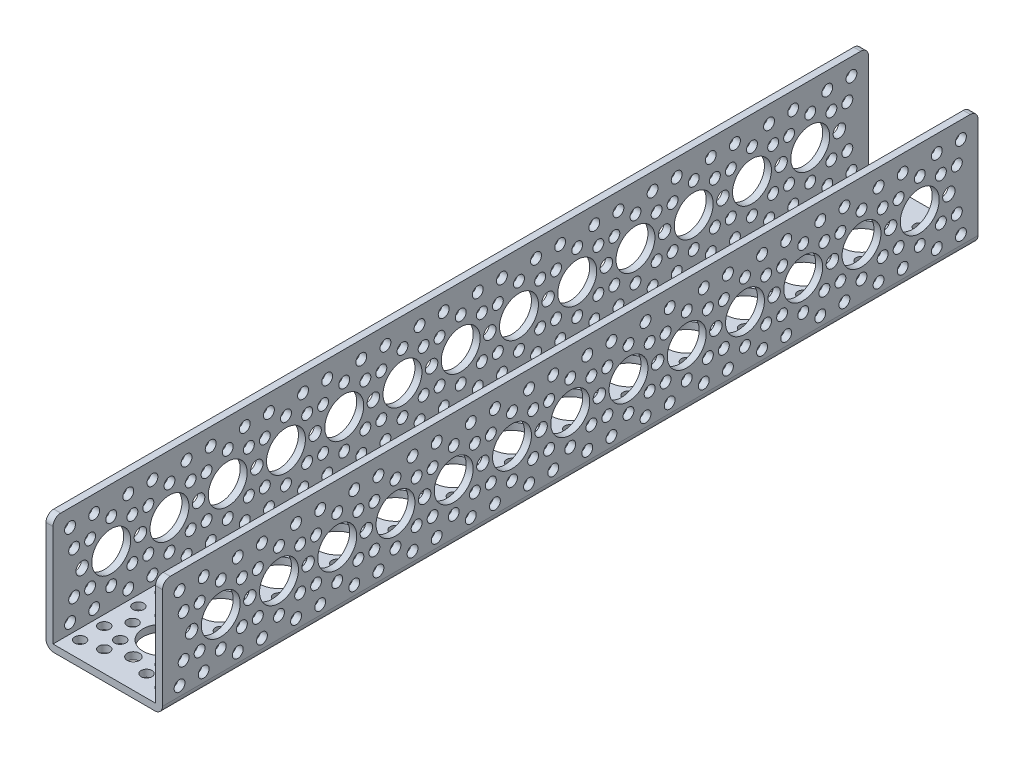
SolidWorks part; units mm, degrees
ref_plane "Front Plane" through (0, 0, 0) normal (0, 0, 1) x (1, 0, 0)
ref_plane "Top Plane" through (0, 0, 0) normal (0, 1, 0) x (1, 0, 0)
ref_plane "Right Plane" through (0, 0, 0) normal (1, 0, 0) x (0, 0, -1)
ref_plane "Plane1" through (0, 0, 0) normal (0, -1, 0) x (1, 0, 0)
sketch "Sketch1" plane through (0, 0, 0) normal (0, -1, 0) x (1, 0, 0)
  line L0 (38.1, 266.7) -> (0, 266.7)
  line L1 (0, 266.7) -> (0, 0)
  line L2 (0, 0) -> (38.1, 0)
  line L3 (38.1, 0) -> (38.1, 266.7)
extrude "Boss-Extrude1" add sketch "Sketch1" against normal blind 38.1
sketch "Sketch2" plane through (0, 0, 266.7) normal (0, 0, 1) x (1, 0, 0)
  line L0 (35.814, 38.1) -> (2.286, 38.1)
  line L1 (2.286, 38.1) -> (2.286, 2.286)
  line L2 (2.286, 2.286) -> (35.814, 2.286)
  line L3 (35.814, 2.286) -> (35.814, 38.1)
extrude "Cut-Extrude1" cut sketch "Sketch2" against normal through all
hole_wizard "Hole1" positions "Sketch4" profile "Sketch3" legacy
sketch "Sketch4" plane through (38.1, 0, 0) normal (1, 0, 0) x (0, 0, -1)
  point P0 (-38.1, 19.05)
  point P1 (-19.05, 19.05)
  point P2 (-57.15, 19.05)
  point P3 (-76.2, 19.05)
  point P4 (-95.25, 19.05)
  point P5 (-114.3, 19.05)
  point P6 (-133.35, 19.05)
  point P7 (-152.4, 19.05)
  point P8 (-171.45, 19.05)
  point P9 (-190.5, 19.05)
  point P10 (-209.55, 19.05)
  point P11 (-228.6, 19.05)
  point P12 (-247.65, 19.05)
sketch "Sketch3" plane through (38.1, 19.05, 38.1) normal (0, 1, 0) x (0, 0, -1)
  line L0 (0, 0) -> (0, 2.286)
  line L1 (0, 2.286) -> (6.3627, 2.286)
  line L2 (6.3627, 2.286) -> (6.3627, 0)
  line L3 (6.3627, 0) -> (0, 0)
  line L4 (0, 110) -> (0, -10) construction
  dimension "Diameter" = 12.7254
  dimension "Depth" = 2.286
hole_wizard "#5 Clearance Hole1" positions "Sketch6" profile "Sketch5" hole size "#5" standard "ANSI Inch"
sketch "Sketch6" plane through (38.1, 0, 0) normal (1, 0, 0) x (0, 0, -1)
  point P0 (-253.2296, 5.5796)
  point P1 (-259.7852, 12.1352)
  point P2 (-253.2296, 32.5204)
  point P3 (-259.7852, 25.9648)
  point P4 (-13.4704, 5.5796)
  point P5 (-6.9148, 12.1352)
  point P6 (-13.4704, 32.5204)
  point P7 (-6.9148, 25.9648)
  point P8 (-234.1796, 5.5796)
  point P9 (-215.1296, 5.5796)
  point P10 (-196.0796, 5.5796)
  point P11 (-177.0296, 5.5796)
  point P12 (-157.9796, 5.5796)
  point P13 (-138.9296, 5.5796)
  point P14 (-119.8796, 5.5796)
  point P15 (-100.8296, 5.5796)
  point P16 (-81.7796, 5.5796)
  point P17 (-62.7296, 5.5796)
  point P18 (-43.6796, 5.5796)
  point P19 (-24.6296, 5.5796)
  point P20 (-234.1796, 32.5204)
  point P21 (-215.1296, 32.5204)
  point P22 (-196.0796, 32.5204)
  point P23 (-177.0296, 32.5204)
  point P24 (-157.9796, 32.5204)
  point P25 (-138.9296, 32.5204)
  point P26 (-119.8796, 32.5204)
  point P27 (-100.8296, 32.5204)
  point P28 (-81.7796, 32.5204)
  point P29 (-62.7296, 32.5204)
  point P30 (-43.6796, 32.5204)
  point P31 (-24.6296, 32.5204)
  point P32 (-261.1204, 5.5796)
  point P33 (-261.1204, 32.5204)
  point P34 (-242.0704, 5.5796)
  point P35 (-242.0704, 32.5204)
  point P36 (-223.0204, 5.5796)
  point P37 (-223.0204, 32.5204)
  point P38 (-203.9704, 5.5796)
  point P39 (-203.9704, 32.5204)
  point P40 (-184.9204, 5.5796)
  point P41 (-184.9204, 32.5204)
  point P42 (-165.8704, 5.5796)
  point P43 (-165.8704, 32.5204)
  point P44 (-146.8204, 5.5796)
  point P45 (-146.8204, 32.5204)
  point P46 (-127.7704, 5.5796)
  point P47 (-127.7704, 32.5204)
  point P48 (-108.7204, 5.5796)
  point P49 (-108.7204, 32.5204)
  point P50 (-89.6704, 5.5796)
  point P51 (-89.6704, 32.5204)
  point P52 (-70.6204, 5.5796)
  point P53 (-70.6204, 32.5204)
  point P54 (-51.5704, 5.5796)
  point P55 (-51.5704, 32.5204)
  point P56 (-240.7352, 12.1352)
  point P57 (-247.65, 9.271)
  point P58 (-254.5648, 12.1352)
  point P59 (-254.5648, 25.9648)
  point P60 (-247.65, 28.829)
  point P61 (-221.6852, 12.1352)
  point P62 (-228.6, 9.271)
  point P63 (-235.5148, 12.1352)
  point P64 (-235.5148, 25.9648)
  point P65 (-228.6, 28.829)
  point P66 (-202.6352, 12.1352)
  point P67 (-209.55, 9.271)
  point P68 (-216.4648, 12.1352)
  point P69 (-216.4648, 25.9648)
  point P70 (-209.55, 28.829)
  point P71 (-183.5852, 12.1352)
  point P72 (-190.5, 9.271)
  point P73 (-197.4148, 12.1352)
  point P74 (-197.4148, 25.9648)
  point P75 (-190.5, 28.829)
  point P76 (-164.5352, 12.1352)
  point P77 (-171.45, 9.271)
  point P78 (-178.3648, 12.1352)
  point P79 (-178.3648, 25.9648)
  point P80 (-171.45, 28.829)
  point P81 (-145.4852, 12.1352)
  point P82 (-152.4, 9.271)
  point P83 (-159.3148, 12.1352)
  point P84 (-159.3148, 25.9648)
  point P85 (-152.4, 28.829)
  point P86 (-126.4352, 12.1352)
  point P87 (-133.35, 9.271)
  point P88 (-140.2648, 12.1352)
  point P89 (-140.2648, 25.9648)
  point P90 (-133.35, 28.829)
  point P91 (-107.3852, 12.1352)
  point P92 (-114.3, 9.271)
  point P93 (-121.2148, 12.1352)
  point P94 (-121.2148, 25.9648)
  point P95 (-114.3, 28.829)
  point P96 (-88.3352, 12.1352)
  point P97 (-95.25, 9.271)
  point P98 (-102.1648, 12.1352)
  point P99 (-102.1648, 25.9648)
  point P100 (-95.25, 28.829)
  point P101 (-69.2852, 12.1352)
  point P102 (-76.2, 9.271)
  point P103 (-83.1148, 12.1352)
  point P104 (-83.1148, 25.9648)
  point P105 (-76.2, 28.829)
  point P106 (-50.2352, 12.1352)
  point P107 (-57.15, 9.271)
  point P108 (-64.0648, 12.1352)
  point P109 (-64.0648, 25.9648)
  point P110 (-57.15, 28.829)
  point P111 (-31.1852, 12.1352)
  point P112 (-38.1, 9.271)
  point P113 (-45.0148, 12.1352)
  point P114 (-45.0148, 25.9648)
  point P115 (-38.1, 28.829)
  point P116 (-240.7352, 25.9648)
  point P117 (-221.6852, 25.9648)
  point P118 (-202.6352, 25.9648)
  point P119 (-183.5852, 25.9648)
  point P120 (-164.5352, 25.9648)
  point P121 (-145.4852, 25.9648)
  point P122 (-126.4352, 25.9648)
  point P123 (-107.3852, 25.9648)
  point P124 (-88.3352, 25.9648)
  point P125 (-69.2852, 25.9648)
  point P126 (-50.2352, 25.9648)
  point P127 (-31.1852, 25.9648)
  point P128 (-32.5204, 5.5796)
  point P129 (-32.5204, 32.5204)
  point P130 (-5.5796, 5.5796)
  point P131 (-5.5796, 32.5204)
  point P132 (-12.1352, 12.1352)
  point P133 (-19.05, 9.271)
  point P134 (-25.9648, 12.1352)
  point P135 (-25.9648, 25.9648)
  point P136 (-19.05, 28.829)
  point P137 (-12.1352, 25.9648)
sketch "Sketch5" plane through (38.1, 5.5796, 253.2296) normal (0, 1, 0) x (0, 0, -1)
  line L0 (0, 0) -> (0, 2.286)
  line L1 (0, 2.286) -> (1.778, 2.286)
  line L2 (1.778, 2.286) -> (1.778, 0)
  line L5 (1.778, 0) -> (0, 0)
  line L11 (0, -6.35) -> (0, 107.95) construction
  dimension "Thru Hole Dia." = 3.556
  dimension "Thru Hole Depth" = 2.286
hole_wizard "#6 Clearance Hole1" positions "Sketch8" profile "Sketch7" hole size "#6" standard "ANSI Inch"
sketch "Sketch8" plane through (38.1, 0, 0) normal (1, 0, 0) x (0, 0, -1)
  point P0 (-257.175, 19.05)
  point P1 (-238.125, 19.05)
  point P2 (-219.075, 19.05)
  point P3 (-200.025, 19.05)
  point P4 (-180.975, 19.05)
  point P5 (-161.925, 19.05)
  point P6 (-142.875, 19.05)
  point P7 (-123.825, 19.05)
  point P8 (-104.775, 19.05)
  point P9 (-85.725, 19.05)
  point P10 (-66.675, 19.05)
  point P11 (-47.625, 19.05)
  point P12 (-28.575, 19.05)
  point P13 (-9.525, 19.05)
sketch "Sketch7" plane through (38.1, 19.05, 257.175) normal (0, 1, 0) x (0, 0, -1)
  line L0 (0, 0) -> (0, 2.286)
  line L1 (0, 2.286) -> (2.032, 2.286)
  line L2 (2.032, 2.286) -> (2.032, 0)
  line L5 (2.032, 0) -> (0, 0)
  line L11 (0, -6.35) -> (0, 107.95) construction
  dimension "Thru Hole Dia." = 4.064
  dimension "Thru Hole Depth" = 2.286
hole_wizard "Hole2" positions "Sketch10" profile "Sketch9" legacy
sketch "Sketch10" plane through (0, 0, 0) normal (0, -1, 0) x (-1, 0, 0)
  point P0 (-19.05, -247.65)
  point P1 (-19.05, -228.6)
  point P2 (-19.05, -209.55)
  point P3 (-19.05, -190.5)
  point P4 (-19.05, -171.45)
  point P5 (-19.05, -152.4)
  point P6 (-19.05, -133.35)
  point P7 (-19.05, -114.3)
  point P8 (-19.05, -95.25)
  point P9 (-19.05, -76.2)
  point P10 (-19.05, -57.15)
  point P11 (-19.05, -38.1)
  point P12 (-19.05, -19.05)
sketch "Sketch9" plane through (19.05, 0, 247.65) normal (1, 0, 0) x (0, 0, -1)
  line L0 (0, 0) -> (0, 38.1)
  line L1 (0, 38.1) -> (6.3627, 38.1)
  line L2 (6.3627, 38.1) -> (6.3627, 0)
  line L3 (6.3627, 0) -> (0, 0)
  line L4 (0, 110) -> (0, -10) construction
  dimension "Diameter" = 12.7254
  dimension "Depth" = 38.1
hole_wizard "#6 Clearance Hole2" positions "Sketch12" profile "Sketch11" hole size "#6" standard "ANSI Inch"
sketch "Sketch12" plane through (0, 0, 0) normal (0, -1, 0) x (-1, 0, 0)
  point P0 (-19.05, -257.175)
  point P1 (-19.05, -238.125)
  point P2 (-19.05, -219.075)
  point P3 (-19.05, -200.025)
  point P4 (-19.05, -180.975)
  point P5 (-19.05, -161.925)
  point P6 (-19.05, -142.875)
  point P7 (-19.05, -123.825)
  point P8 (-19.05, -104.775)
  point P9 (-19.05, -85.725)
  point P10 (-19.05, -66.675)
  point P11 (-19.05, -47.625)
  point P12 (-19.05, -28.575)
  point P13 (-19.05, -9.525)
sketch "Sketch11" plane through (19.05, 0, 257.175) normal (1, 0, 0) x (0, 0, -1)
  line L0 (0, 0) -> (0, 38.1)
  line L1 (0, 38.1) -> (2.032, 38.1)
  line L2 (2.032, 38.1) -> (2.032, 0)
  line L5 (2.032, 0) -> (0, 0)
  line L11 (0, -6.35) -> (0, 107.95) construction
  dimension "Thru Hole Dia." = 4.064
  dimension "Thru Hole Depth" = 38.1
hole_wizard "#5 Clearance Hole2" positions "Sketch14" profile "Sketch13" hole size "#5" standard "ANSI Inch"
sketch "Sketch14" plane through (0, 0, 0) normal (0, -1, 0) x (-1, 0, 0)
  point P0 (-5.5796, -261.1204)
  point P1 (-5.5796, -253.2296)
  point P2 (-12.1352, -259.7852)
  point P3 (-32.5204, -261.1204)
  point P4 (-32.5204, -253.2296)
  point P5 (-25.9648, -259.7852)
  point P6 (-5.5796, -242.0704)
  point P7 (-5.5796, -234.1796)
  point P8 (-32.5204, -242.0704)
  point P9 (-32.5204, -234.1796)
  point P10 (-5.5796, -223.0204)
  point P11 (-5.5796, -215.1296)
  point P12 (-32.5204, -223.0204)
  point P13 (-32.5204, -215.1296)
  point P14 (-5.5796, -203.9704)
  point P15 (-5.5796, -196.0796)
  point P16 (-32.5204, -203.9704)
  point P17 (-32.5204, -196.0796)
  point P18 (-5.5796, -184.9204)
  point P19 (-5.5796, -177.0296)
  point P20 (-32.5204, -184.9204)
  point P21 (-32.5204, -177.0296)
  point P22 (-5.5796, -165.8704)
  point P23 (-5.5796, -157.9796)
  point P24 (-32.5204, -165.8704)
  point P25 (-32.5204, -157.9796)
  point P26 (-5.5796, -146.8204)
  point P27 (-5.5796, -138.9296)
  point P28 (-32.5204, -146.8204)
  point P29 (-32.5204, -138.9296)
  point P30 (-5.5796, -127.7704)
  point P31 (-5.5796, -119.8796)
  point P32 (-32.5204, -127.7704)
  point P33 (-32.5204, -119.8796)
  point P34 (-5.5796, -108.7204)
  point P35 (-5.5796, -100.8296)
  point P36 (-32.5204, -108.7204)
  point P37 (-32.5204, -100.8296)
  point P38 (-5.5796, -89.6704)
  point P39 (-5.5796, -81.7796)
  point P40 (-32.5204, -89.6704)
  point P41 (-32.5204, -81.7796)
  point P42 (-5.5796, -70.6204)
  point P43 (-5.5796, -62.7296)
  point P44 (-32.5204, -70.6204)
  point P45 (-32.5204, -62.7296)
  point P46 (-5.5796, -51.5704)
  point P47 (-5.5796, -43.6796)
  point P48 (-32.5204, -51.5704)
  point P49 (-32.5204, -43.6796)
  point P50 (-12.1352, -240.7352)
  point P51 (-9.271, -247.65)
  point P52 (-12.1352, -254.5648)
  point P53 (-25.9648, -254.5648)
  point P54 (-28.829, -247.65)
  point P55 (-25.9648, -240.7352)
  point P56 (-12.1352, -221.6852)
  point P57 (-9.271, -228.6)
  point P58 (-12.1352, -235.5148)
  point P59 (-25.9648, -235.5148)
  point P60 (-28.829, -228.6)
  point P61 (-25.9648, -221.6852)
  point P62 (-12.1352, -202.6352)
  point P63 (-9.271, -209.55)
  point P64 (-12.1352, -216.4648)
  point P65 (-25.9648, -216.4648)
  point P66 (-28.829, -209.55)
  point P67 (-25.9648, -202.6352)
  point P68 (-12.1352, -183.5852)
  point P69 (-9.271, -190.5)
  point P70 (-12.1352, -197.4148)
  point P71 (-25.9648, -197.4148)
  point P72 (-28.829, -190.5)
  point P73 (-25.9648, -183.5852)
  point P74 (-12.1352, -164.5352)
  point P75 (-9.271, -171.45)
  point P76 (-12.1352, -178.3648)
  point P77 (-25.9648, -178.3648)
  point P78 (-28.829, -171.45)
  point P79 (-25.9648, -164.5352)
  point P80 (-12.1352, -145.4852)
  point P81 (-9.271, -152.4)
  point P82 (-12.1352, -159.3148)
  point P83 (-25.9648, -159.3148)
  point P84 (-28.829, -152.4)
  point P85 (-25.9648, -145.4852)
  point P86 (-12.1352, -126.4352)
  point P87 (-9.271, -133.35)
  point P88 (-12.1352, -140.2648)
  point P89 (-25.9648, -140.2648)
  point P90 (-28.829, -133.35)
  point P91 (-25.9648, -126.4352)
  point P92 (-12.1352, -107.3852)
  point P93 (-9.271, -114.3)
  point P94 (-12.1352, -121.2148)
  point P95 (-25.9648, -121.2148)
  point P96 (-28.829, -114.3)
  point P97 (-25.9648, -107.3852)
  point P98 (-12.1352, -88.3352)
  point P99 (-9.271, -95.25)
  point P100 (-12.1352, -102.1648)
  point P101 (-25.9648, -102.1648)
  point P102 (-28.829, -95.25)
  point P103 (-25.9648, -88.3352)
  point P104 (-12.1352, -69.2852)
  point P105 (-9.271, -76.2)
  point P106 (-12.1352, -83.1148)
  point P107 (-25.9648, -83.1148)
  point P108 (-28.829, -76.2)
  point P109 (-25.9648, -69.2852)
  point P110 (-12.1352, -50.2352)
  point P111 (-9.271, -57.15)
  point P112 (-12.1352, -64.0648)
  point P113 (-25.9648, -64.0648)
  point P114 (-28.829, -57.15)
  point P115 (-25.9648, -50.2352)
  point P116 (-9.271, -38.1)
  point P117 (-12.1352, -45.0148)
  point P118 (-25.9648, -45.0148)
  point P119 (-28.829, -38.1)
  point P120 (-5.5796, -32.5204)
  point P121 (-5.5796, -24.6296)
  point P122 (-12.1352, -31.1852)
  point P123 (-32.5204, -32.5204)
  point P124 (-32.5204, -24.6296)
  point P125 (-25.9648, -31.1852)
  point P126 (-5.5796, -5.5796)
  point P127 (-5.5796, -13.4704)
  point P128 (-12.1352, -6.9148)
  point P129 (-32.5204, -5.5796)
  point P130 (-32.5204, -13.4704)
  point P131 (-25.9648, -6.9148)
  point P132 (-12.1352, -12.1352)
  point P133 (-9.271, -19.05)
  point P134 (-12.1352, -25.9648)
  point P135 (-25.9648, -25.9648)
  point P136 (-28.829, -19.05)
  point P137 (-25.9648, -12.1352)
sketch "Sketch13" plane through (5.5796, 0, 261.1204) normal (1, 0, 0) x (0, 0, -1)
  line L0 (0, 0) -> (0, 38.1)
  line L1 (0, 38.1) -> (1.778, 38.1)
  line L2 (1.778, 38.1) -> (1.778, 0)
  line L5 (1.778, 0) -> (0, 0)
  line L11 (0, -6.35) -> (0, 107.95) construction
  dimension "Thru Hole Dia." = 3.556
  dimension "Thru Hole Depth" = 38.1
hole_wizard "Hole3" positions "Sketch16" profile "Sketch15" legacy
sketch "Sketch16" plane through (0, 0, 0) normal (-1, 0, 0) x (0, 0, 1)
  point P0 (38.1, 19.05)
  point P1 (19.05, 19.05)
  point P2 (57.15, 19.05)
  point P3 (76.2, 19.05)
  point P4 (95.25, 19.05)
  point P5 (114.3, 19.05)
  point P6 (133.35, 19.05)
  point P7 (152.4, 19.05)
  point P8 (171.45, 19.05)
  point P9 (190.5, 19.05)
  point P10 (209.55, 19.05)
  point P11 (228.6, 19.05)
  point P12 (247.65, 19.05)
sketch "Sketch15" plane through (0, 19.05, 38.1) normal (0, 1, 0) x (0, 0, 1)
  line L0 (0, 0) -> (0, 38.1)
  line L1 (0, 38.1) -> (6.3627, 38.1)
  line L2 (6.3627, 38.1) -> (6.3627, 0)
  line L3 (6.3627, 0) -> (0, 0)
  line L4 (0, 110) -> (0, -10) construction
  dimension "Diameter" = 12.7254
  dimension "Depth" = 38.1
hole_wizard "#5 Clearance Hole3" positions "Sketch18" profile "Sketch17" hole size "#5" standard "ANSI Inch"
sketch "Sketch18" plane through (0, 0, 0) normal (-1, 0, 0) x (0, 0, 1)
  point P0 (253.2296, 5.5796)
  point P1 (259.7852, 12.1352)
  point P2 (253.2296, 32.5204)
  point P3 (259.7852, 25.9648)
  point P4 (13.4704, 5.5796)
  point P5 (6.9148, 12.1352)
  point P6 (13.4704, 32.5204)
  point P7 (6.9148, 25.9648)
  point P8 (234.1796, 5.5796)
  point P9 (215.1296, 5.5796)
  point P10 (196.0796, 5.5796)
  point P11 (177.0296, 5.5796)
  point P12 (157.9796, 5.5796)
  point P13 (138.9296, 5.5796)
  point P14 (119.8796, 5.5796)
  point P15 (100.8296, 5.5796)
  point P16 (81.7796, 5.5796)
  point P17 (62.7296, 5.5796)
  point P18 (43.6796, 5.5796)
  point P19 (24.6296, 5.5796)
  point P20 (234.1796, 32.5204)
  point P21 (215.1296, 32.5204)
  point P22 (196.0796, 32.5204)
  point P23 (177.0296, 32.5204)
  point P24 (157.9796, 32.5204)
  point P25 (138.9296, 32.5204)
  point P26 (119.8796, 32.5204)
  point P27 (100.8296, 32.5204)
  point P28 (81.7796, 32.5204)
  point P29 (62.7296, 32.5204)
  point P30 (43.6796, 32.5204)
  point P31 (24.6296, 32.5204)
  point P32 (261.1204, 5.5796)
  point P33 (261.1204, 32.5204)
  point P34 (242.0704, 5.5796)
  point P35 (242.0704, 32.5204)
  point P36 (223.0204, 5.5796)
  point P37 (223.0204, 32.5204)
  point P38 (203.9704, 5.5796)
  point P39 (203.9704, 32.5204)
  point P40 (184.9204, 5.5796)
  point P41 (184.9204, 32.5204)
  point P42 (165.8704, 5.5796)
  point P43 (165.8704, 32.5204)
  point P44 (146.8204, 5.5796)
  point P45 (146.8204, 32.5204)
  point P46 (127.7704, 5.5796)
  point P47 (127.7704, 32.5204)
  point P48 (108.7204, 5.5796)
  point P49 (108.7204, 32.5204)
  point P50 (89.6704, 5.5796)
  point P51 (89.6704, 32.5204)
  point P52 (70.6204, 5.5796)
  point P53 (70.6204, 32.5204)
  point P54 (51.5704, 5.5796)
  point P55 (51.5704, 32.5204)
  point P56 (240.7352, 12.1352)
  point P57 (247.65, 9.271)
  point P58 (254.5648, 12.1352)
  point P59 (254.5648, 25.9648)
  point P60 (247.65, 28.829)
  point P61 (221.6852, 12.1352)
  point P62 (228.6, 9.271)
  point P63 (235.5148, 12.1352)
  point P64 (235.5148, 25.9648)
  point P65 (228.6, 28.829)
  point P66 (202.6352, 12.1352)
  point P67 (209.55, 9.271)
  point P68 (216.4648, 12.1352)
  point P69 (216.4648, 25.9648)
  point P70 (209.55, 28.829)
  point P71 (183.5852, 12.1352)
  point P72 (190.5, 9.271)
  point P73 (197.4148, 12.1352)
  point P74 (197.4148, 25.9648)
  point P75 (190.5, 28.829)
  point P76 (164.5352, 12.1352)
  point P77 (171.45, 9.271)
  point P78 (178.3648, 12.1352)
  point P79 (178.3648, 25.9648)
  point P80 (171.45, 28.829)
  point P81 (145.4852, 12.1352)
  point P82 (152.4, 9.271)
  point P83 (159.3148, 12.1352)
  point P84 (159.3148, 25.9648)
  point P85 (152.4, 28.829)
  point P86 (126.4352, 12.1352)
  point P87 (133.35, 9.271)
  point P88 (140.2648, 12.1352)
  point P89 (140.2648, 25.9648)
  point P90 (133.35, 28.829)
  point P91 (107.3852, 12.1352)
  point P92 (114.3, 9.271)
  point P93 (121.2148, 12.1352)
  point P94 (121.2148, 25.9648)
  point P95 (114.3, 28.829)
  point P96 (88.3352, 12.1352)
  point P97 (95.25, 9.271)
  point P98 (102.1648, 12.1352)
  point P99 (102.1648, 25.9648)
  point P100 (95.25, 28.829)
  point P101 (69.2852, 12.1352)
  point P102 (76.2, 9.271)
  point P103 (83.1148, 12.1352)
  point P104 (83.1148, 25.9648)
  point P105 (76.2, 28.829)
  point P106 (50.2352, 12.1352)
  point P107 (57.15, 9.271)
  point P108 (64.0648, 12.1352)
  point P109 (64.0648, 25.9648)
  point P110 (57.15, 28.829)
  point P111 (31.1852, 12.1352)
  point P112 (38.1, 9.271)
  point P113 (45.0148, 12.1352)
  point P114 (45.0148, 25.9648)
  point P115 (38.1, 28.829)
  point P116 (240.7352, 25.9648)
  point P117 (221.6852, 25.9648)
  point P118 (202.6352, 25.9648)
  point P119 (183.5852, 25.9648)
  point P120 (164.5352, 25.9648)
  point P121 (145.4852, 25.9648)
  point P122 (126.4352, 25.9648)
  point P123 (107.3852, 25.9648)
  point P124 (88.3352, 25.9648)
  point P125 (69.2852, 25.9648)
  point P126 (50.2352, 25.9648)
  point P127 (31.1852, 25.9648)
  point P128 (32.5204, 5.5796)
  point P129 (32.5204, 32.5204)
  point P130 (5.5796, 5.5796)
  point P131 (5.5796, 32.5204)
  point P132 (12.1352, 12.1352)
  point P133 (19.05, 9.271)
  point P134 (25.9648, 12.1352)
  point P135 (25.9648, 25.9648)
  point P136 (19.05, 28.829)
  point P137 (12.1352, 25.9648)
sketch "Sketch17" plane through (0, 5.5796, 253.2296) normal (0, 1, 0) x (0, 0, 1)
  line L0 (0, 0) -> (0, 38.1)
  line L1 (0, 38.1) -> (1.778, 38.1)
  line L2 (1.778, 38.1) -> (1.778, 0)
  line L5 (1.778, 0) -> (0, 0)
  line L11 (0, -6.35) -> (0, 107.95) construction
  dimension "Thru Hole Dia." = 3.556
  dimension "Thru Hole Depth" = 38.1
hole_wizard "#6 Clearance Hole3" positions "Sketch20" profile "Sketch19" hole size "#6" standard "ANSI Inch"
sketch "Sketch20" plane through (0, 0, 0) normal (-1, 0, 0) x (0, 0, 1)
  point P0 (257.175, 19.05)
  point P1 (238.125, 19.05)
  point P2 (219.075, 19.05)
  point P3 (200.025, 19.05)
  point P4 (180.975, 19.05)
  point P5 (161.925, 19.05)
  point P6 (142.875, 19.05)
  point P7 (123.825, 19.05)
  point P8 (104.775, 19.05)
  point P9 (85.725, 19.05)
  point P10 (66.675, 19.05)
  point P11 (47.625, 19.05)
  point P12 (28.575, 19.05)
  point P13 (9.525, 19.05)
sketch "Sketch19" plane through (0, 19.05, 257.175) normal (0, 1, 0) x (0, 0, 1)
  line L0 (0, 0) -> (0, 38.1)
  line L1 (0, 38.1) -> (2.032, 38.1)
  line L2 (2.032, 38.1) -> (2.032, 0)
  line L5 (2.032, 0) -> (0, 0)
  line L11 (0, -6.35) -> (0, 107.95) construction
  dimension "Thru Hole Dia." = 4.064
  dimension "Thru Hole Depth" = 38.1
fillet "Fillet1" radius 2.54 6 edges at (1.143, 38.1, 266.7) (36.957, 38.1, 266.7) (36.957, 38.1, 0) (38.1, 0, 133.35) (1.143, 38.1, 0) (0, 0, 133.35) tangent propagation no
